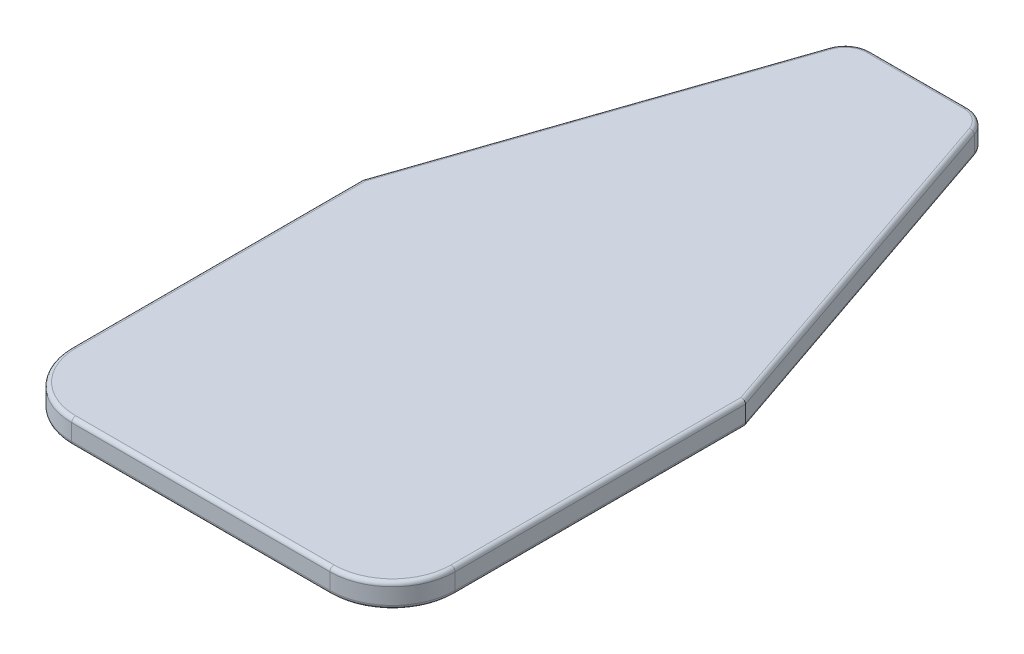
SolidWorks part; units mm, degrees
material "Pine"
ref_plane "Front Plane" through (0, 0, 0) normal (0, 0, 1) x (1, 0, 0)
ref_plane "Top Plane" through (0, 0, 0) normal (0, 1, 0) x (1, 0, 0)
ref_plane "Right Plane" through (0, 0, 0) normal (1, 0, 0) x (0, 0, -1)
sketch "Sketch1" plane through (0, 0, 0) normal (0, 1, 0) x (1, 0, 0)
  line L0 (-101.6, -24.3645) -> (101.6, -24.3645)
  line L1 (-38.1, 540.7855) -> (38.1, 540.7855)
  line L2 (0, 540.7855) -> (0, -24.3645) construction
  line L3 (150.8125, 253.448) -> (57.15, 527.1697)
  line L4 (-150.8125, 253.448) -> (-57.15, 527.1697)
  line L5 (-150.8125, 253.448) -> (0, 253.448) construction
  line L6 (150.8125, 253.448) -> (0, 253.448) construction
  line L7 (-150.8125, 24.848) -> (-150.8125, 253.448)
  line L8 (150.8125, 24.848) -> (150.8125, 253.448)
  line L9 (-150.8125, 24.848) -> (0, 24.848) construction
  line L10 (150.8125, 24.848) -> (0, 24.848) construction
  arc A0 (101.6, -24.3645) -> (150.8125, 24.848) centre (101.6, 24.848) ccw
  arc A1 (-150.8125, 24.848) -> (-101.6, -24.3645) centre (-101.6, 24.848) ccw
  arc A2 (57.15, 527.1697) -> (38.1, 540.7855) centre (38.1, 520.6511) ccw
  arc A3 (-38.1, 540.7855) -> (-57.15, 527.1697) centre (-38.1, 520.6511) ccw
  dimension "D2" = 114.3
  dimension "D6" = 76.2
  dimension "D7" = 49.2125
  dimension "D8" = 20.1344
  dimension "D1" = 203.2
  dimension "D3" = 228.6
  dimension "D4" = 565.15
  dimension "D5" = 301.625
extrude "Boss-Extrude1" add sketch "Sketch1" along normal blind 19.05
fillet "Fillet1" radius 3.175 10 edges at (-103.9813, 19.05, -390.3089) (-49.8078, 19.05, -537.0316) (0, 19.05, -540.7855) (49.8078, 19.05, -537.0316) (-150.8125, 19.05, -139.148) (-136.3985, 19.05, 9.9505) (0, 19.05, 24.3645) (136.3985, 19.05, 9.9505) (103.9812, 19.05, -390.3089) (150.8125, 19.05, -139.148)
fillet "Fillet2" radius 3.175 10 edges at (103.9812, 0, -390.3089) (49.8078, 0, -537.0316) (0, 0, -540.7855) (-49.8078, 0, -537.0316) (-150.8125, 0, -139.148) (-136.3985, 0, 9.9505) (150.8125, 0, -139.148) (136.3985, 0, 9.9505) (-103.9813, 0, -390.3089) (0, 0, 24.3645)
sketch "Sketch5" plane through (0, 19.05, 0) normal (0, 1, 0) x (1, 0, 0)
  line L0 (38.1, 537.6105) -> (-38.1, 537.6105) construction
  line L1 (0, -21.1895) -> (-0.003, 542.4026) construction
  line L2 (-43.3215, 507.7584) -> (43.3215, 507.7584) construction
  line L3 (-101.6, -21.1895) -> (101.6, -21.1895) construction
  line L4 (43.3215, 507.7584) -> (60.4365, 507.7584) construction
  line L5 (147.6375, 252.9198) -> (54.146, 526.1418) construction
  line L6 (-43.3215, 507.7584) -> (-60.4365, 507.7584) construction
  line L7 (-54.146, 526.1418) -> (-147.6375, 252.9198) construction
  line B0 (-35.109, 447.4484) -> (35.2377, 518.3442) construction
  line B1 (-35.1059, 518.2113) -> (35.109, 447.4484) construction
  arc B2 (-24.9328, 526.498) -> (24.9268, 526.498) centre (-0.003, 542.4026) ccw
  arc B3 (-43.3215, 507.7584) -> (-24.9328, 526.498) centre (7.5558, 476.2258) cw
  arc B4 (24.9268, 526.498) -> (43.3215, 507.7584) centre (-2.6466, 481.0344) cw
  arc B5 (43.3215, 507.7584) -> (43.2864, 457.8401) centre (60.0594, 482.7875) ccw
  arc B6 (43.2864, 457.8401) -> (24.9269, 439.51) centre (-3.0428, 485.8841) cw
  arc B7 (-24.9914, 439.5451) -> (-43.2864, 457.8401) centre (3.0881, 485.9196) cw
  arc B8 (-43.3215, 507.7584) -> (-43.2864, 457.8401) centre (-60.0645, 482.7875) cw
  arc B9 (-24.9914, 439.5451) -> (24.9269, 439.51) centre (-0.0437, 423.2596) cw
  circle B10 centre (-30.052, 512.8835) radius 2.25
  circle B11 centre (30.0521, 512.8835) radius 2.25
  circle B12 centre (30.0519, 452.7794) radius 2.25
  circle B13 centre (-30.0527, 452.7791) radius 2.25
  circle B14 centre (0.0248, 482.837) radius 12.27
  line B15 (59.1543, -0.8785) -> (129.501, 70.0173) construction
  line B16 (59.1575, 69.8844) -> (129.3724, -0.8785) construction
  arc B17 (69.3306, 78.1711) -> (119.1902, 78.1711) centre (94.2604, 94.0757) ccw
  arc B18 (50.9418, 59.4315) -> (69.3306, 78.1711) centre (101.8192, 27.8988) cw
  arc B19 (119.1902, 78.1711) -> (137.5848, 59.4315) centre (91.6168, 32.7074) cw
  arc B20 (137.5848, 59.4315) -> (137.5497, 9.5132) centre (154.3228, 34.4605) ccw
  arc B21 (137.5497, 9.5132) -> (119.1902, -8.8169) centre (91.2205, 37.5572) cw
  arc B22 (69.2719, -8.7818) -> (50.9769, 9.5132) centre (97.3515, 37.5927) cw
  arc B23 (50.9418, 59.4315) -> (50.9769, 9.5132) centre (34.1989, 34.4605) cw
  arc B24 (69.2719, -8.7818) -> (119.1902, -8.8169) centre (94.2197, -25.0673) cw
  circle B25 centre (64.2114, 64.5566) radius 2.25
  circle B26 centre (124.3154, 64.5566) radius 2.25
  circle B27 centre (124.3152, 4.4525) radius 2.25
  circle B28 centre (64.2106, 4.4522) radius 2.25
  circle B29 centre (94.2881, 34.5101) radius 12.27
  line B30 (-59.1545, -0.8791) -> (-129.502, 70.0159) construction
  line B31 (-59.1584, 69.8838) -> (-129.3726, -0.8798) construction
  arc B32 (-69.3316, 78.1704) -> (-119.1912, 78.1699) centre (-94.2616, 94.0747) cw
  arc B33 (-50.9427, 59.4309) -> (-69.3316, 78.1704) centre (-101.8197, 27.8978) ccw
  arc B34 (-119.1912, 78.1699) -> (-137.5857, 59.43) centre (-91.6173, 32.7065) ccw
  arc B35 (-137.5857, 59.43) -> (-137.5501, 9.5117) centre (-154.3234, 34.4589) cw
  arc B36 (-137.5501, 9.5117) -> (-119.1904, -8.8182) centre (-91.2211, 37.5562) ccw
  arc B37 (-69.2721, -8.7826) -> (-50.9773, 9.5126) centre (-97.3521, 37.5917) ccw
  arc B38 (-50.9427, 59.4309) -> (-50.9773, 9.5126) centre (-34.1994, 34.4602) ccw
  arc B39 (-69.2721, -8.7826) -> (-119.1904, -8.8182) centre (-94.2196, -25.0683) ccw
  circle B40 centre (-64.2123, 64.5559) radius 2.25
  circle B41 centre (-124.3163, 64.5553) radius 2.25
  circle B42 centre (-124.3155, 4.4512) radius 2.25
  circle B43 centre (-64.2109, 4.4515) radius 2.25
  circle B44 centre (-94.2887, 34.5091) radius 12.27
  line B45 (144.3193, 78.0251) -> (128.3193, 78.0251)
  line B46 (144.3193, 78.0251) -> (144.3193, 168.0251)
  line B47 (128.3193, 78.0251) -> (128.3193, 168.0251)
  circle B48 centre (136.3192, 84.2751) radius 2.25
  circle B49 centre (136.3192, 161.7751) radius 2.25
  line B50 (-144.3203, 78.0236) -> (-128.3203, 78.0237)
  line B51 (-144.3203, 78.0236) -> (-144.3212, 168.0236)
  line B52 (-128.3203, 78.0237) -> (-128.3212, 168.0237)
  circle B53 centre (-136.3203, 84.2736) radius 2.25
  circle B54 centre (-136.3211, 161.7737) radius 2.25
  dimension "D1" = 11.1125
  dimension "D2" = 11.1125
sketch_block_instance "Block2-1"
sketch_block "Block2"
sketch_block_instance "Block2-6"
sketch_block_instance "Block2-7"
sketch_block_instance "Block1-1"
sketch_block "Block1"
sketch_block_instance "Block1-2"
sketch "Sketch6" plane through (0, 0, 0) normal (0, -1, 0) x (1, 0, 0)
  line L0 (0, -10.4775) -> (0, 10.4775) construction
  line L1 (36.5, -529.0479) -> (-36.5, -529.0479)
  line L2 (36.5, -529.0479) -> (36.5, -437.0479)
  line L3 (36.5, -437.0479) -> (-36.5, -437.0479)
  line L4 (-36.5, -529.0479) -> (-36.5, -437.0479)
  line L5 (36.5, -529.0479) -> (-36.5, -437.0479) construction
  line L6 (36.5, -437.0479) -> (-36.5, -529.0479) construction
  point P0 (0, -483.0479)
  dimension "D1" = 73
  dimension "D2" = 92
